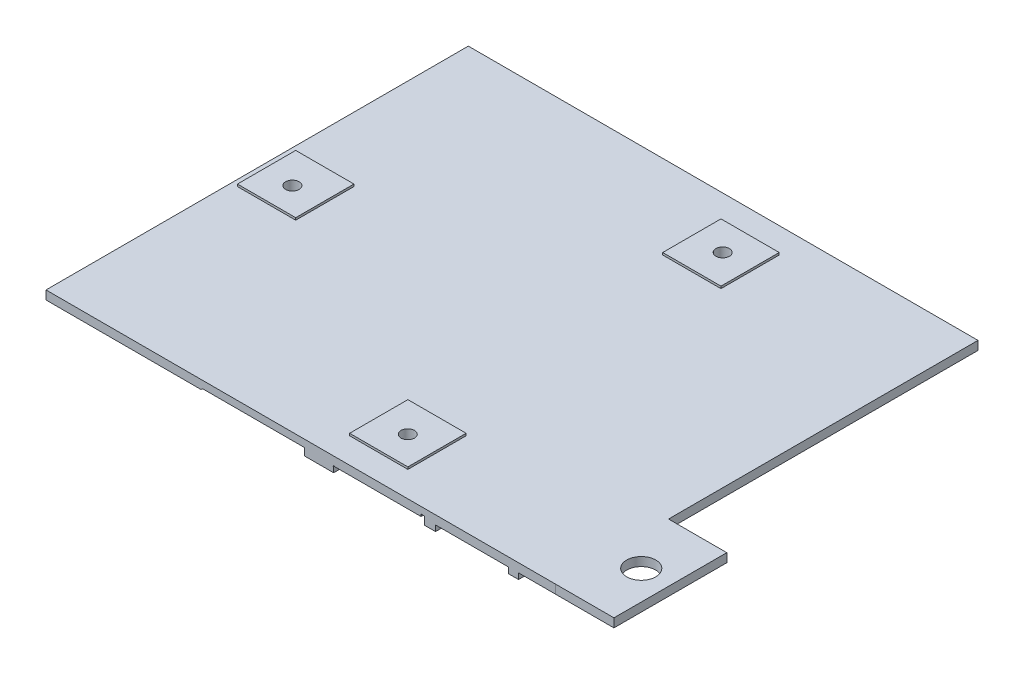
SolidWorks part; units mm, degrees
note: The reader was unsure of these and kept them because the rebuilt part matched: shared geometry of "草图15<3>".
material "灰铸铁"
ref_plane "前视基准面" through (0, 0, 0) normal (0, 0, 1) x (1, 0, 0)
ref_plane "上视基准面" through (0, 0, 0) normal (0, 1, 0) x (1, 0, 0)
ref_plane "右视基准面" through (0, 0, 0) normal (1, 0, 0) x (0, 0, -1)
sketch "草图1" plane through (0, 0, 0) normal (0, 1, 0) x (1, 0, 0)
  line L1 (350, -290) -> (-350, -290)
  line L2 (350, -290) -> (350, 290)
  line L3 (350, 290) -> (-350, 290)
  line L4 (-350, -290) -> (-350, 290)
  line L5 (350, -290) -> (-350, 290) construction
  line L6 (350, 290) -> (-350, -290) construction
  point P0 (0, 0)
  dimension "D1" = 700
  dimension "D2" = 580
extrude "凸台-拉伸1" add sketch "草图1" along normal blind 20
sketch "草图2" plane through (0, 20, 0) normal (0, 1, 0) x (1, 0, 0)
  line L0 (350, -290) -> (430, -290.0005)
  line L1 (350, -290) -> (350, 290) construction
  line L2 (430, -135.0005) -> (430, -290.0005)
  line L3 (430, -135.0005) -> (350, -135.0005)
  line L4 (350, -290) -> (350, -290.0005)
  line L5 (350, -135.0005) -> (350, -290.0005)
  line L8 (-350, 290) -> (-350, -290)
  line L9 (-350, -290) -> (350, -290)
  line L10 (350, -290) -> (350, 290)
  line L11 (350, 290) -> (-350, 290)
  line L12 (-350, 290) -> (-350, -290)
  line L13 (-350, -290) -> (350, -290)
  line L15 (350, 290) -> (-350, 290)
  dimension "D1" = 80
  dimension "D2" = 155
  dimension "D4" = 0
extrude "凸台-拉伸2" add sketch "草图2" against normal blind 12
sketch "草图3" plane through (0, 20, 0) normal (0, 1, 0) x (1, 0, 0)
  line L0 (513.2416, -212.5005) -> (389.7059, -212.5005) construction
  line L1 (350, 97.2162) -> (350, -249.0109) construction
  line L2 (350, -135.0005) -> (350, 290) construction
  line L3 (350, -135.0005) -> (350, 290) construction
  line L4 (390, -135.0005) -> (390, -50135.0005) construction
  line L5 (430, -135.0005) -> (350, -135.0005) construction
  circle A0 centre (390, -212.5005) radius 20
  point P14 (390, -135.0005)
  dimension "D1" = 40
  dimension "D2" = 77.5
extrude "切除-拉伸1" cut sketch "草图3" against normal up to next
sketch "草图4" plane through (0, 0, -290) normal (0, 0, -1) x (-1, 0, 0)
  line L0 (-170, 0) -> (-170, 8)
  line L1 (-350, 0) -> (350, 0) construction
  line L2 (-165, 8) -> (-46.0607, 8)
  line L3 (-45, 6.9393) -> (-45, 0)
  line L4 (-45, 0) -> (-170, 0)
  line L5 (-350, 20) -> (-350, 0) construction
  line L6 (-46.0607, 8) -> (-45.3536, 8.7071)
  line L7 (-45.3536, 8.7071) -> (-44.2929, 7.6464)
  line L8 (-44.2929, 7.6464) -> (-45, 6.9393)
  line L9 (-170, 8) -> (-170, 11)
  line L10 (-170, 11) -> (-165, 11)
  line L11 (-165, 11) -> (-165, 8)
  dimension "D1" = 1.5
  dimension "D2" = 125
  dimension "D3" = 180
  dimension "D4" = 1
  dimension "D5" = 1
  dimension "D6" = 8
  dimension "D7" = 45
  dimension "D8" = 3
  dimension "D9" = 5
extrude "切除-拉伸2" cut sketch "草图4" against normal up to next
sketch "草图5" plane through (0, 0, -290) normal (0, 0, -1) x (-1, 0, 0)
  line L0 (-5, 0) -> (-5, 10)
  line L1 (-45, 0) -> (350, 0) construction
  line L2 (-5, 10) -> (135, 10)
  line L5 (167, 0) -> (-5, 0)
  line L6 (-45, 0) -> (-45, 6.9393) construction
  line L7 (135, 10) -> (137, 8)
  line L8 (137, 8) -> (350, 8)
  line L9 (350, 20) -> (350, 0) construction
  line L10 (350, 8) -> (350, 0)
  line L11 (350, 0) -> (167, 0)
  dimension "D1" = 10
  dimension "D2" = 40
  dimension "D3" = 140
  dimension "D4" = 8
  dimension "D5" = 135
extrude "切除-拉伸3" cut sketch "草图5" against normal up to next
sketch "草图6" plane through (0, 0, -290) normal (0, 0, -1) x (-1, 0, 0)
  line L0 (-185, 0) -> (-185, 8)
  line L1 (-350, 0) -> (-170, 0) construction
  line L2 (-185, 8) -> (-285, 8)
  line L3 (-285, 8) -> (-285, 0)
  line L4 (-285, 0) -> (-185, 0)
  line L5 (-170, 11) -> (-170, 0) construction
  dimension "D1" = 8
  dimension "D2" = 15
  dimension "D3" = 100
extrude "切除-拉伸4" cut sketch "草图6" against normal up to next
sketch "草图7" plane through (185, 0, 0) normal (1, 0, 0) x (0, 0, -1)
  line L1 (290, 0) -> (290, 8) construction
  circle A0 centre (200, 4) radius 2
  circle A1 centre (180, 4) radius 2
  circle A2 centre (160, 4) radius 2
  circle A3 centre (140, 4) radius 2
  circle A4 centre (120, 4) radius 2
  circle A6 centre (100, 4) radius 2 [skipped]
  dimension "D1" = 4
  dimension "D3" = 4
  dimension "D5" = 4
  dimension "D2" = 90
  dimension "D4" = 20
  dimension "D6" = 20
  dimension "D7" = 4
extrude "切除-拉伸5" cut sketch "草图7" against normal up to next
sketch "草图8" plane through (185, 0, 0) normal (1, 0, 0) x (0, 0, -1)
  line L0 (-294.538, 4) -> (-286.4878, 4) construction
  circle A0 centre (-125, 4) radius 2
  circle A1 centre (120, 4) radius 2 construction
  dimension "D1" = 4
  dimension "D2" = 245
extrude "切除-拉伸6" cut sketch "草图8" against normal up to next
pattern_linear "阵列(线性)1" count 5 spacing 20 along (0, 0, 1) of "切除-拉伸6"
sketch "草图9" plane through (0, 0, 290) normal (0, 0, 1) x (1, 0, 0)
  line L0 (299, 0) -> (299, 8)
  line L1 (285, 0) -> (350, 0) construction
  line L2 (299, 8) -> (430, 8)
  line L3 (430, 8) -> (430, 20) construction
  line L4 (430, 8) -> (430, 0)
  line L5 (430, 0) -> (299, 0)
  line L6 (285, 0) -> (285, 8) construction
  dimension "D1" = 14
  dimension "D2" = 8
extrude "切除-拉伸7" cut sketch "草图9" against normal up to next
sketch "草图13" plane through (0, 8, 0) normal (0, -1, 0) x (1, 0, 0)
  circle A0 centre (-245, 137.5) radius 5.5
  circle A1 centre (-245, 197.5) radius 5.5
  circle A2 centre (-145, 197.5) radius 5.5
  circle A3 centre (-145, 137.5) radius 5.5
extrude "切除-拉伸10" cut sketch "草图13" against normal blind 5
pattern_linear "阵列(线性)2" count 2 spacing 300 along (1, 0, 0) of "切除-拉伸10"
pattern_linear "阵列(线性)3" count 2 spacing 325 along (0, 0, -1) of "切除-拉伸10", "阵列(线性)2"
sketch "草图15" plane through (0, 20, 0) normal (0, 1, 0) x (1, 0, 0)
  line L0 (-350, -290) -> (350, -290) construction
  line L1 (32, -175) -> (112, -175)
  line L2 (32, -175) -> (32, -255)
  line L3 (32, -255) -> (112, -255)
  line L4 (112, -175) -> (112, -255)
  line L5 (-350, 290) -> (-350, -290) construction
  line L6 (0, 0) -> (438.1219, 0) construction
  line L7 (112, 175) -> (112, 255)
  line L8 (32, 175) -> (112, 175)
  line L9 (32, 175) -> (32, 255)
  line L10 (32, 255) -> (112, 255)
  line L12 (-341.4596, 44.3995) -> (-261.4596, 44.3995)
  line L13 (-341.4596, 44.3995) -> (-341.4596, -35.6005)
  line L14 (-341.4596, -35.6005) -> (-261.4596, -35.6005)
  line L15 (-261.4596, 44.3995) -> (-261.4596, -35.6005)
  circle A0 centre (73.0857, -216.2472) radius 9.25
  circle A1 centre (73.0857, 216.2472) radius 9.25
  dimension "D5" = 18.5
  dimension "D1" = 80
  dimension "D2" = 80
  dimension "D3" = 35
  dimension "D4" = 382
  dimension "D6" = 80
  dimension "D7" = 80
extrude "凸台-拉伸3" add sketch "草图15" along normal blind 3 contours L9 L10 L7 L8 | L2 L3 L4 L1 | L13 L14 L15 L12
sketch "草图16" plane through (0, 23, 0) normal (0, 1, 0) x (1, 0, 0)
  circle A0 centre (-301.9143, 0.2591) radius 9.25
  dimension "D1" = 18.5
extrude "切除-拉伸11" cut sketch "草图16" against normal through all
extrude "切除-拉伸12" cut sketch "草图15<3>" against normal mid plane 30 contours A0 | A1
sketch "草图15<3>" plane through (0, 20, 0) normal (0, 1, 0) x (1, 0, 0) same geometry as "草图15"
